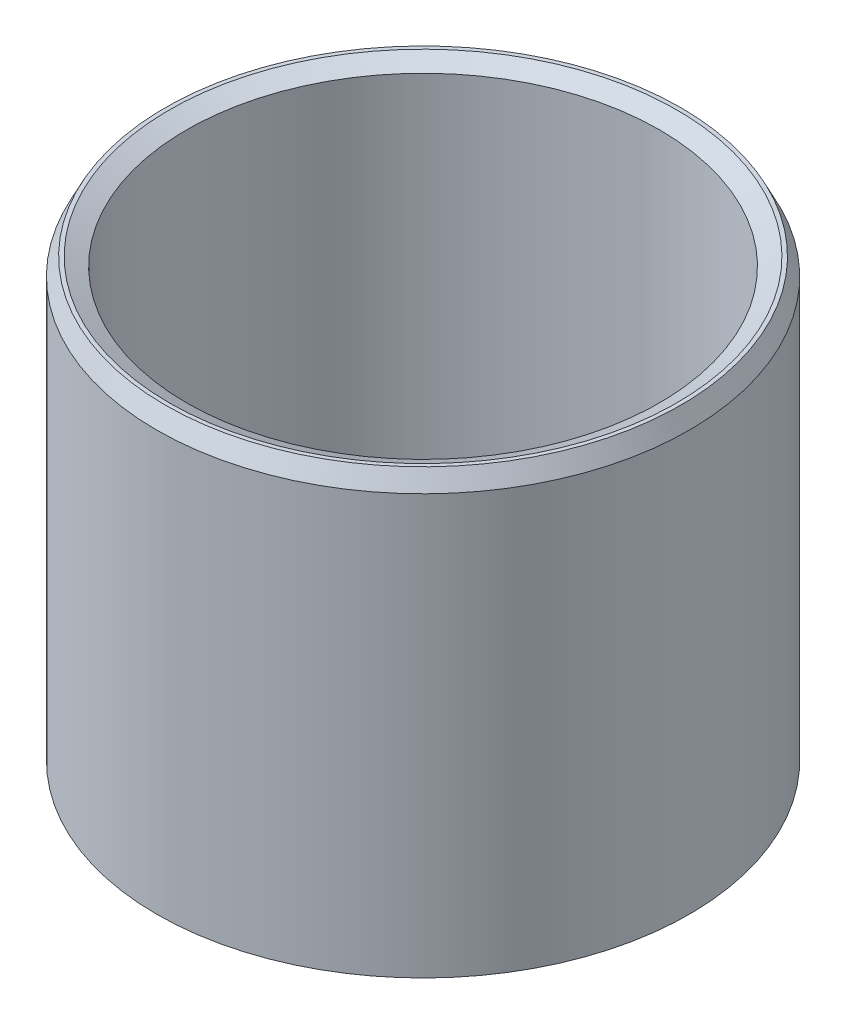
SolidWorks part; units mm, degrees
ref_plane "Front Plane" through (0, 0, 0) normal (0, 0, 1) x (1, 0, 0)
ref_plane "Top Plane" through (0, 0, 0) normal (0, 1, 0) x (1, 0, 0)
ref_plane "Right Plane" through (0, 0, 0) normal (1, 0, 0) x (0, 0, -1)
sketch "Sketch1" plane through (0, 0, 0) normal (0, 1, 0) x (1, 0, 0)
  circle A0 centre (0, 0) radius 60
  dimension "SLEEVE_OD" = 120
extrude "Boss-Extrude1" add sketch "Sketch1" along normal blind 100.3017
sketch "Sketch2" plane through (0, 0, 0) normal (0, 1, 0) x (1, 0, 0)
  circle A0 centre (0, 0) radius 53.2768
  dimension "BORE_D" = 106.5536
extrude "Cut-Extrude1" cut sketch "Sketch2" along normal through all
chamfer "Chamfer1" distance 3.8952 angle 26.495 4 edges at (0, 100.3017, 53.2768) (0, 0, 53.2768) (0, 0, 60) (0, 100.3017, 60) first distance on face at (0, 100.3017, 53.2768) first distance on face at (0, 0, 53.2768) first distance on face at (0, 100.3017, 60)
